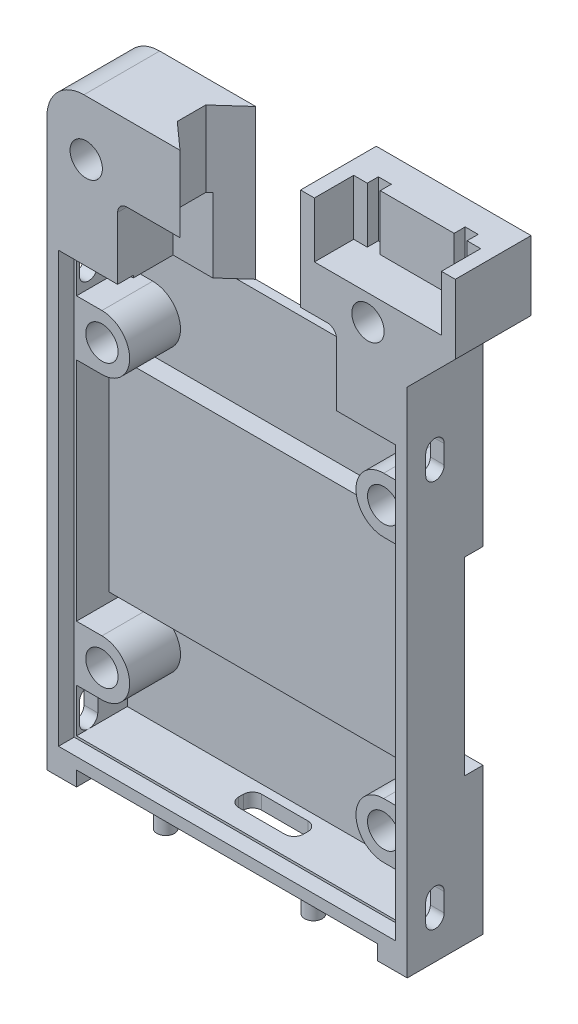
SolidWorks part; units mm, degrees
ref_plane "Front Plane" through (0, 0, 0) normal (0, 0, 1) x (1, 0, 0)
ref_plane "Top Plane" through (0, 0, 0) normal (0, 1, 0) x (1, 0, 0)
ref_plane "Right Plane" through (0, 0, 0) normal (1, 0, 0) x (0, 0, -1)
sketch "Sketch1" plane through (0, 0, 0) normal (0, 0, 1) x (1, 0, 0)
  line L0 (15.25, -20.35) -> (18, -20.35)
  line L1 (-19.5, -32.6) -> (19.5, -32.6)
  line L2 (-19.5, -32.6) -> (-19.5, 31.1)
  line L3 (-19.5, 31.1) -> (19.5, 31.1)
  line L4 (19.5, -32.6) -> (19.5, 31.1)
  line L5 (-15.25, -20.35) -> (-18, -20.35)
  line L6 (15.25, -26.35) -> (18, -26.35)
  line L7 (6.95, 31.1) -> (-15.5, 31.1) construction
  line L8 (-18, -31.1) -> (-18, 29.6)
  line L9 (-18, 29.6) -> (18, 29.6)
  line L10 (18, -31.1) -> (18, 29.6)
  line L11 (-18, -31.1) -> (18, -31.1)
  line L12 (-18, 14.9) -> (18, 14.9)
  line L13 (7.85, 14.9) -> (-4.95, 14.9) construction
  line L14 (-15.25, 4.15) -> (-18, 4.15)
  line L15 (-15.25, 10.15) -> (-18, 10.15)
  line L16 (15.25, 10.15) -> (18, 10.15)
  line L17 (15.25, 4.15) -> (18, 4.15)
  line L18 (-15.25, -26.35) -> (-18, -26.35)
  line L19 (19.5, -34.2) -> (19.5, -18.35) construction
  line L20 (-19.5, -34.2) -> (-19.5, -18.35) construction
  line L21 (15.3, -32.6) -> (-15.3, -32.6) construction
  line L22 (0, 31.1) -> (0, -32.6) construction
  line L23 (9.45, 26.9) -> (24.7, 26.9)
  line L24 (9.45, 26.9) -> (9.45, 33.9)
  line L25 (9.45, 33.9) -> (24.7, 33.9)
  line L26 (24.7, 26.9) -> (24.7, 33.9)
  line L27 (18, 29.6) -> (19.5, 31.1) construction
  line L28 (18.75, 30.35) -> (0, 30.35) construction
  line L29 (9.45, 26.9) -> (7.95, 26.9) construction
  line L30 (-7.95, 31.1) -> (7.95, 31.1)
  line L31 (-7.95, 31.1) -> (-7.95, 29.6)
  line L32 (-7.95, 29.6) -> (7.95, 29.6)
  line L33 (7.95, 31.1) -> (7.95, 29.6)
  line L34 (-7.95, 31.1) -> (7.95, 29.6) construction
  line L35 (-7.95, 29.6) -> (7.95, 31.1) construction
  line L36 (7.95, 26.9) -> (7.95, 29.6) construction
  line L37 (18, 29.6) -> (19.5, 29.6) construction
  line L38 (24.7, 26.4) -> (19.5, 21.2)
  line L39 (9.45, 33.9) -> (7.95, 33.9)
  line L40 (23.2, 33.9) -> (23.2, 26.9)
  line L41 (7.95, 33.9) -> (7.95, 31.1)
  line L42 (24.7, 30.4) -> (23.2, 30.4) construction
  line L43 (24.7, 26.9) -> (19.5, 26.9)
  line L44 (24.7, 26.9) -> (24.7, 26.4)
  line L45 (24.7, 26.4) -> (19.5, 26.4)
  line L46 (19.5, 26.9) -> (19.5, 26.4)
  arc A1 (-15.5, 31.1) -> (-19.5, 27.1) centre (-15.5, 27.1) ccw construction
  arc A3 (-15.5, 31.1) -> (-19.5, 27.1) centre (-15.5, 27.1) ccw
  arc A4 (-15.5, 29.6) -> (-18, 27.1) centre (-15.5, 27.1) ccw
  circle A6 centre (-15.25, -23.35) radius 1.75
  circle A7 centre (15.25, -23.35) radius 1.75
  circle A8 centre (-15.25, 7.15) radius 1.75
  circle A9 centre (15.25, 7.15) radius 1.75
  circle A10 centre (15.25, 25.15) radius 1.75
  circle A11 centre (-15.25, 25.15) radius 1.75
  circle A12 centre (-15.25, -23.35) radius 3
  circle A13 centre (15.25, -23.35) radius 3
  circle A14 centre (15.25, 7.15) radius 3
  circle A15 centre (-15.25, 7.15) radius 3
  dimension "D2" = 1.5
  dimension "D4" = 6
  dimension "D3" = 3.5
  dimension "D5" = 13.75
  dimension "D6" = 15.9
  dimension "D7" = 7
  dimension "D8" = 45
  dimension "D9" = 0.5
  dimension "D1" = 1.5
extrude "Base shape" add sketch "Sketch1" along normal up to surface (8.2 mm away) contours L3 A3 L2 L1 L4 A15 L8 L9 L10 A14 A13 L11 A12 | A15 L15 L8 | A15 L8 L14 | A12 L5 L8 | A12 L8 L18 | A13 L10 L0 | A13 L6 L10 | A14 L10 L16 | A14 L17 L10 | L9 A4 L8 L12 L10 A11 A10 | A4 L9 L8 | L10 A13 | L10 A13 A7 | A12 L8 A6 | L8 A12 | A15 L8 A8 | L8 A15 | L10 A14 | L10 A14 A9 | L33 L3 L31 L9 | L3 L33 L9 L24 | L24 L9 L10 L23 L4 L3 | L24 L23 L10 L9 | L23 L26 L25 L24 L3 L4 | L23 L4 | L3 L24 | L25 L40 L23 L26 | L38 L45 L4 region at (16.8481, -20.9099, 0) region at (17.3601, -20.8437, 0) region at (18.7469, -8.1, 0) region at (17.3601, -25.8563, 0) region at (18.1004, -23.35, 0) region at (17.3601, 4.6437, 0) region at (16.8481, 4.7099, 0) region at (18.1004, 7.15, 0) region at (17.3601, 9.6563, 0) region at (-17.3601, -25.8563, 0) region at (-0.6044, 21.831, 0) region at (-18.1004, -23.35, 0) region at (-17.9169, -23.35, 0) region at (13.725, 28.25, 0) region at (15.3803, 29.9053, 0) region at (-17.3601, -20.8437, 0) region at (22.1, 26.65, 0) region at (17.77, 31.4935, 0) region at (-17.3601, 9.6563, 0) region at (-17.4416, 29.0416, 0) region at (8.7, 30.35, 0) region at (21.2333, 24.6667, 0) region at (23.95, 30.4, 0) region at (-16.8481, 9.5901, 0) region at (-18.1004, 7.15, 0) region at (-17.3601, 4.6437, 0) region at (0, 30.35, 0) region at (8.7, 32.5, 0)
sketch "Sketch3" plane through (19.5, 0, 0) normal (1, 0, 0) x (0, 0, -1)
  line L1 (0, -18.35) -> (-2, -18.35)
  line L2 (0, -18.35) -> (0, 2.15)
  line L3 (0, 2.15) -> (-2, 2.15)
  line L4 (-2, -18.35) -> (-2, 2.15)
  line L5 (0, -18.35) -> (2, -18.35) construction
  line L6 (0, 2.15) -> (2, 2.15) construction
  line L7 (0, -32.6) -> (0, 21.2) construction
  dimension "D1" = 2
extrude "Strap cut" cut sketch "Sketch3" against normal through all
sketch "Sketch4" plane through (0, 31.1, 0) normal (0, 1, 0) x (1, 0, 0)
  line L2 (7.95, 0) -> (-5.0998, 0)
  line L4 (-15.5, 0) -> (7.95, 0) construction
  line L5 (-15.5, -8.2) -> (7.95, -8.2) construction
  line L6 (7.95, -8.2) -> (-5.0998, -8.2)
  line L12 (7.95, -8.3) -> (7.95, 0.1)
  line L13 (7.95, 0.1) -> (-4.9883, 0.1)
  line L14 (-4.9883, 0.1) -> (-7.95, -2.5553)
  line L15 (-7.95, -2.5553) -> (-7.95, -5.6447)
  line L16 (-7.95, -5.6447) -> (-4.9883, -8.3)
  line L17 (-4.9883, -8.3) -> (7.95, -8.3)
  line L18 (7.95, -8.3) -> (7.95, 0.1)
  line L19 (7.95, 0.1) -> (-4.9883, 0.1)
  line L20 (-4.9883, 0.1) -> (-7.95, -2.5553)
  line L21 (-7.95, -2.5553) -> (-7.95, -5.6447)
  line L22 (-7.95, -5.6447) -> (-4.9883, -8.3)
  line L23 (-4.9883, -8.3) -> (7.95, -8.3)
  dimension "D1" = 0.1
extrude "XT60 cut" cut sketch "Sketch4" against normal up to next contours L21 L22 L18 L20 region at (0.4142, 31.1, 4.1)
sketch "Sketch5" plane through (19.5, 0, 0) normal (1, 0, 0) x (0, 0, -1)
  line L1 (-8.2, -32.6) -> (-8.2, 21.2) construction
  line L2 (-6.2, -31.1) -> (-4.2, -31.1)
  line L3 (-6.2, -31.1) -> (-6.2, -27.1)
  line L4 (-6.2, -27.1) -> (-4.2, -27.1)
  line L5 (-4.2, -31.1) -> (-4.2, -27.1)
  line L6 (-8.2, -31.1) -> (0, -31.1) construction
  line L7 (-8.2, 14.9) -> (0, 14.9) construction
  line L8 (-6.2, 14.9) -> (-4.2, 14.9)
  line L9 (-6.2, 14.9) -> (-6.2, 10.9)
  line L10 (-6.2, 10.9) -> (-4.2, 10.9)
  line L11 (-4.2, 14.9) -> (-4.2, 10.9)
  line L14 (-5.2, -27.1) -> (-5.2, -31.1) construction
  line L15 (-5.2, 14.9) -> (-5.2, 10.9) construction
  circle A0 centre (-5.2, -28.1) radius 1
  circle A1 centre (-5.2, -30.1) radius 1
  circle A2 centre (-5.2, 13.9) radius 1
  circle A3 centre (-5.2, 11.9) radius 1
  point P20 (-5.2, -29.1)
  point P31 (-5.2, 12.9)
  dimension "D3" = 4
  dimension "D1" = 2
  dimension "D2" = 2
extrude "Power wires cut" cut sketch "Sketch5" against normal through all contours A2 | A3 | A3 A2 L9 | A3 L11 A2 | A1 | A0 | A1 L5 A0 | A1 A0 L3 region at (19.5, -30.1, 5.2) region at (19.5, -29.1, 5.9766) region at (19.5, -29.1, 4.4234) region at (19.5, -28.1, 5.2) region at (19.5, 13.9, 5.2) region at (19.5, 12.9, 5.9766) region at (19.5, 12.9, 4.4234) region at (19.5, 11.9, 5.2)
sketch "Sketch6" plane through (0, 0, 8.2) normal (0, 0, 1) x (1, 0, 0)
  line L0 (-7.85, 15.9) -> (-7.85, 21.9) construction
  line L1 (-8.85, 22.9) -> (-10.85, 22.9) construction
  line L2 (-11.85, 15.9) -> (-11.85, 21.9) construction
  line L3 (-8.85, 14.9) -> (-10.85, 14.9) construction
  line L4 (-7.85, 15.9) -> (-7.85, 21.9)
  line L5 (-8.85, 22.9) -> (-10.85, 22.9)
  line L6 (-11.85, 15.9) -> (-11.85, 21.9)
  line L7 (-8.85, 14.9) -> (-10.85, 14.9)
  line L8 (7.85, 15.9) -> (7.85, 21.9) construction
  line L9 (8.85, 22.9) -> (10.85, 22.9) construction
  line L10 (11.85, 15.9) -> (11.85, 21.9) construction
  line L11 (8.85, 14.9) -> (10.85, 14.9) construction
  line L12 (7.85, 15.9) -> (7.85, 21.9)
  line L13 (8.85, 22.9) -> (10.85, 22.9)
  line L14 (11.85, 15.9) -> (11.85, 21.9)
  line L15 (8.85, 14.9) -> (10.85, 14.9)
  line L17 (-11.85, 15.9) -> (-7.85, 15.9)
  line L18 (-11.85, 15.9) -> (-11.85, 14.9)
  line L19 (-11.85, 14.9) -> (-7.85, 14.9)
  line L20 (-7.85, 15.9) -> (-7.85, 14.9)
  line L22 (11.85, 15.9) -> (7.85, 15.9)
  line L23 (11.85, 15.9) -> (11.85, 14.9)
  line L24 (11.85, 14.9) -> (7.85, 14.9)
  line L25 (7.85, 15.9) -> (7.85, 14.9)
  line L26 (-18, 14.9) -> (-5.0998, 14.9) construction
  line L27 (11.85, 21.9) -> (7.85, 21.9)
  line L28 (11.85, 21.9) -> (11.85, 22.9)
  line L29 (11.85, 22.9) -> (7.85, 22.9)
  line L30 (7.85, 21.9) -> (7.85, 22.9)
  line L31 (-8.85, 22.9) -> (7.95, 22.9)
  line L32 (-8.85, 22.9) -> (-8.85, 14.9)
  line L33 (-8.85, 14.9) -> (7.95, 14.9)
  line L34 (7.95, 22.9) -> (7.95, 14.9)
  line L35 (7.95, 14.9) -> (18, 14.9) construction
  line L36 (7.95, 14.9) -> (7.95, 33.9) construction
  arc A0 (-8.85, 14.9) -> (-7.85, 15.9) centre (-8.85, 15.9) ccw construction
  arc A1 (-7.85, 21.9) -> (-8.85, 22.9) centre (-8.85, 21.9) ccw construction
  arc A2 (-10.85, 22.9) -> (-11.85, 21.9) centre (-10.85, 21.9) ccw construction
  arc A3 (-11.85, 15.9) -> (-10.85, 14.9) centre (-10.85, 15.9) ccw construction
  arc A4 (-8.85, 14.9) -> (-7.85, 15.9) centre (-8.85, 15.9) ccw
  arc A5 (-7.85, 21.9) -> (-8.85, 22.9) centre (-8.85, 21.9) ccw
  arc A6 (-10.85, 22.9) -> (-11.85, 21.9) centre (-10.85, 21.9) ccw
  arc A7 (-11.85, 15.9) -> (-10.85, 14.9) centre (-10.85, 15.9) ccw
  arc A8 (8.85, 22.9) -> (7.85, 21.9) centre (8.85, 21.9) ccw construction
  arc A9 (11.85, 21.9) -> (10.85, 22.9) centre (10.85, 21.9) ccw construction
  arc A10 (10.85, 14.9) -> (11.85, 15.9) centre (10.85, 15.9) ccw construction
  arc A11 (7.85, 15.9) -> (8.85, 14.9) centre (8.85, 15.9) ccw construction
  arc A12 (8.85, 22.9) -> (7.85, 21.9) centre (8.85, 21.9) ccw
  arc A13 (11.85, 21.9) -> (10.85, 22.9) centre (10.85, 21.9) ccw
  arc A14 (10.85, 14.9) -> (11.85, 15.9) centre (10.85, 15.9) ccw
  arc A15 (7.85, 15.9) -> (8.85, 14.9) centre (8.85, 15.9) ccw
  line M1 (7.95, 33.9) -> (7.95, 14.9)
  line M15 (-5.0998, 14.9) -> (-5.0998, 31.1)
extrude "IO wires cut" cut sketch "Sketch6" against normal blind 6 contours L33 L25 L12 L30 L31 M15 | A5 L4 L20 L31 M15 | L4 A5 L32 L17 | L5 A6 L6 L17 L32 | A7 L18 | L17 A7 L32 | L32 A4 L17 | A4 L20 | A12 L29 L30 M1 | L27 L12 L22 M1 | L22 A15 M1 | A15 L25 L24 L34 | A15 L34 | A15 A14 L22 M1 | A14 L23 | L14 L27 L22 M1 | L27 A13 L13 A12 L34 | A12 L29 M1 region at (-8.3587, 19.2964, 8.2) region at (-8.4256, 15.4756, 8.2) region at (-6.4903, 18.9365, 8.2) region at (-8.0734, 15.1234, 8.2) region at (-10.2516, 15.4213, 8.2) region at (-10.3368, 19.3662, 8.2) region at (-11.6266, 15.1234, 8.2) region at (1.3751, 18.9, 8.2) region at (7.8959, 15.2606, 8.2) region at (7.8959, 22.5394, 8.2) region at (8.1604, 15.056, 8.2) region at (7.9, 18.9, 8.2) region at (7.9098, 15.7354, 8.2) region at (8.1604, 22.744, 8.2) region at (9.8661, 15.4307, 8.2) region at (9.9, 18.9, 8.2) region at (9.8661, 22.3693, 8.2) region at (11.6266, 15.1234, 8.2)
sketch "Sketch7" plane through (-18, 0, 0) normal (1, 0, 0) x (0, 0, -1)
  line L6 (0, -18.35) -> (0, -20.35)
  line L7 (-2, -18.35) -> (0, -18.35)
  line L8 (-2, 2.15) -> (-2, -18.35)
  line L9 (0, 2.15) -> (-2, 2.15)
  line L12 (0, 3.15) -> (-3, 3.15)
  line L13 (-3, 3.15) -> (-3, -19.35)
  line L14 (-3, -19.35) -> (-1, -19.35)
  line L15 (-1, -19.35) -> (-1, -20.35)
  line L16 (-1, -20.35) -> (0, -20.35)
  line L17 (0, 3.15) -> (-1, 3.15)
  line L19 (0, -31.1) -> (-1, -31.1)
  line L22 (0, -31.1) -> (0, -20.35)
  line L23 (0, -20.35) -> (-1, -20.35)
  line L24 (-1, -31.1) -> (-1, -20.35)
  line L25 (0, 3.15) -> (0, 14.9)
  line L26 (0, 14.9) -> (-1, 14.9)
  line L27 (-1, 3.15) -> (-1, 14.9)
  line L28 (-5.2, 14.9) -> (0, 14.9) construction
  line L31 (0, -20.35) -> (0, -18.35) construction
  line L32 (0, 2.15) -> (-2, 2.15) construction
  line M48 (0, -20.35) -> (0, -18.35)
  line M49 (0, -18.35) -> (-2, -18.35)
  line M50 (-2, -18.35) -> (-2, 2.15)
  line M51 (-2, 2.15) -> (0, 2.15)
  line M52 (0, 2.15) -> (0, 4.15)
  line M53 (0, 4.15) -> (-8.2, 4.15)
  line M55 (-8.2, -20.35) -> (0, -20.35)
  dimension "D1" = 1
extrude "Bottom" add sketch "Sketch7" along normal up to surface (36 mm away) contours L27 L25 L26 M53 | L27 L12 M52 M53 | L14 L15 L12 L13 M55 M48 M49 M50 M51 M52 | L24 L19 L22 M55 region at (-18, -8.5273, 2.2091) region at (-18, -25.725, 0.5) region at (-18, 3.65, 0.5) region at (-18, 9.525, 0.5) up to face at (18, -8.1, 2.55)
sketch "Sketch9" plane through (0, 0, 0) normal (0, 0, -1) x (-1, 0, 0)
  circle A0 centre (-15.25, -23.35) radius 1.75 construction
  circle A1 centre (-15.25, 7.15) radius 1.75 construction
  circle A2 centre (15.25, 7.15) radius 1.75 construction
  circle A3 centre (15.25, -23.35) radius 1.75 construction
  circle A4 centre (-15.25, -23.35) radius 1.75
  circle A5 centre (-15.25, 7.15) radius 1.75
  circle A6 centre (15.25, 7.15) radius 1.75
  circle A7 centre (15.25, -23.35) radius 1.75
extrude "Bottom holes" cut sketch "Sketch9" against normal up to next
sketch "Sketch8" plane through (0, 0, 8.2) normal (0, 0, 1) x (1, 0, 0)
  line L0 (-6.2152, 14.9) -> (-18, 14.9) construction
  line L1 (-18.25, 15.15) -> (18.25, 15.15)
  line L2 (-18.25, 15.15) -> (-18.25, -31.35)
  line L3 (-18.25, -31.35) -> (18.25, -31.35)
  line L4 (18.25, 15.15) -> (18.25, -31.35)
  line L5 (-18, 14.9) -> (-18.25, 14.9) construction
  line L6 (-18, 14.9) -> (-18, 15.15) construction
  line L7 (18, 14.9) -> (18.25, 14.9) construction
  line L8 (-18, -31.1) -> (-18, -31.35) construction
  dimension "D1" = 0.25
extrude "PCB cut" cut sketch "Sketch8" against normal blind 1.7
sketch "Sketch11" plane through (0, -32.6, 0) normal (0, -1, 0) x (1, 0, 0)
  line L0 (19.5, 8.2) -> (19.5, 0) construction
  line L1 (-19.5, 8.2) -> (19.5, 8.2)
  line L2 (-19.5, 8.2) -> (-19.5, -1.8)
  line L3 (-19.5, -1.8) -> (19.5, -1.8)
  line L4 (19.5, 8.2) -> (19.5, -1.8)
  line L5 (-19.5, 3.2) -> (19.5, 3.2) construction
  line L6 (0, -1.8) -> (0, 8.2) construction
  line L8 (-2.5, 4.45) -> (2.5, 4.45)
  line L9 (-3.5, 3.45) -> (-3.5, 2.95)
  line L10 (-2.5, 1.95) -> (2.5, 1.95)
  line L11 (3.5, 3.45) -> (3.5, 2.95)
  line L12 (-3.5, 4.45) -> (3.5, 1.95) construction
  line L13 (-3.5, 1.95) -> (3.5, 4.45) construction
  arc A0 (2.5, 4.45) -> (3.5, 3.45) centre (2.5, 3.45) cw
  arc A1 (2.5, 1.95) -> (3.5, 2.95) centre (2.5, 2.95) ccw
  arc A2 (-3.5, 2.95) -> (-2.5, 1.95) centre (-2.5, 2.95) ccw
  arc A3 (-2.5, 4.45) -> (-3.5, 3.45) centre (-2.5, 3.45) ccw
  point P11 (0, 3.2)
  dimension "D4" = 1
  dimension "D1" = 10
  dimension "D2" = 7
  dimension "D3" = 2.5
extrude "Ledbar wires cut" cut sketch "Sketch11" against normal up to next contours L8 A3 L9 A2 L10 A1 L11 A0 region at (0, -32.6, 3.2)
sketch "Sketch13" plane through (0, -32.6, 0) normal (0, -1, 0) x (1, 0, 0)
  line L0 (-19.5, 8.2) -> (19.5, 8.2) construction
  line L1 (19.5, 0) -> (16.3, 0)
  line L2 (19.5, 0) -> (19.5, 8.2)
  line L3 (19.5, 8.2) -> (16.3, 8.2)
  line L4 (16.3, 0) -> (16.3, 8.2)
  line L5 (16.1, -1.8) -> (16.1, 8.2) construction
  line L6 (0, 8.2) -> (0, 0) construction
  line L7 (-19.5, 0) -> (-16.3, 0)
  line L8 (-19.5, 0) -> (-19.5, 8.2)
  line L9 (-19.5, 8.2) -> (-16.3, 8.2)
  line L10 (-16.3, 0) -> (-16.3, 8.2)
  dimension "D1" = 0.2
extrude "Ledbar sides" add sketch "Sketch13" along normal blind 1.6
sketch "Sketch14" plane through (0, -32.6, 0) normal (0, -1, 0) x (1, 0, 0)
  circle A0 centre (8, 6.85) radius 0.95
  circle A1 centre (-8, 6.85) radius 0.95
  dimension "D1" = 1.9
extrude "Ledbar mounts" add sketch "Sketch14" along normal blind 2
sketch "Sketch16" plane through (0, 33.9, 0) normal (0, 1, 0) x (1, 0, 0)
  line L0 (7.95, -6.075) -> (24.7, -6.075) construction
  line L1 (7.95, -8.2) -> (24.7, -8.2) construction
  line L2 (21.725, -2.75) -> (20.325, -2.75)
  line L3 (20.325, -3.95) -> (20.325, -2.75)
  line L4 (9.45, -3.95) -> (23.2, -3.95)
  line L5 (9.45, -3.95) -> (9.45, -8.2)
  line L6 (9.45, -8.2) -> (23.2, -8.2)
  line L7 (23.2, -3.95) -> (23.2, -8.2)
  line L8 (9.45, -3.95) -> (23.2, -8.2) construction
  line L9 (9.45, -8.2) -> (23.2, -3.95) construction
  line L10 (24.7, -8.2) -> (24.7, 0) construction
  line L11 (7.95, -8.2) -> (7.95, 0) construction
  line L12 (16.325, -8.2) -> (16.325, -3.95) construction
  line L13 (11.625, -2.75) -> (11.625, -3.95) construction
  line L14 (10.925, -3.95) -> (12.325, -3.95)
  line L15 (10.925, -3.95) -> (10.925, -2.75)
  line L16 (10.925, -2.75) -> (12.325, -2.75)
  line L17 (12.325, -3.95) -> (12.325, -2.75)
  line L18 (10.925, -2.75) -> (10.925, -8.2) construction
  line L19 (21.725, -3.95) -> (21.725, -2.75)
  point P6 (16.325, -6.075)
  dimension "D1" = 13.75
  dimension "D2" = 4.25
  dimension "D3" = 1.4
  dimension "D4" = 1.2
  dimension "D5" = 4.7
extrude "Balance plug cut" cut sketch "Sketch16" against normal blind 6 contours L7 L4 L5 L6 | L4 L17 L16 L15 | L4 L19 L2 L3 region at (21.025, 33.9, 3.35) region at (16.325, 33.9, 6.075) region at (11.625, 33.9, 3.35)
sketch "Sketch10" [suppressed] plane through (0, 0, 2) normal (0, 0, -1) x (-1, 0, 0)
  line L0 (0, 2.15) -> (0, -18.35) construction
  line L1 (19.5, 2.15) -> (-19.5, 2.15) construction
  line L2 (19.5, -18.35) -> (-19.5, -18.35) construction
  line L3 (19.5, 2.15) -> (19.5, -18.35) construction
  line L4 (-19.5, 1.15) -> (19.5, 1.15)
  line L5 (-19.5, 1.15) -> (-19.5, 0.65)
  line L6 (-19.5, 0.65) -> (19.5, 0.65)
  line L7 (19.5, 1.15) -> (19.5, 0.65)
  line L8 (-19.5, 1.15) -> (19.5, 0.65) construction
  line L9 (-19.5, 0.65) -> (19.5, 1.15) construction
  line L10 (-19.5, 2.15) -> (19.5, 2.15) construction
  line L11 (-19.5, -1.35) -> (19.5, -1.35)
  line L12 (19.5, -0.85) -> (19.5, -1.35)
  line L13 (-19.5, -0.85) -> (19.5, -0.85)
  line L14 (-19.5, -0.85) -> (-19.5, -1.35)
  line L15 (-19.5, -3.35) -> (19.5, -3.35)
  line L16 (19.5, -2.85) -> (19.5, -3.35)
  line L17 (-19.5, -2.85) -> (19.5, -2.85)
  line L18 (-19.5, -2.85) -> (-19.5, -3.35)
  line L19 (-19.5, -5.35) -> (19.5, -5.35)
  line L20 (19.5, -4.85) -> (19.5, -5.35)
  line L21 (-19.5, -4.85) -> (19.5, -4.85)
  line L22 (-19.5, -4.85) -> (-19.5, -5.35)
  line L23 (-19.5, -7.35) -> (19.5, -7.35)
  line L24 (19.5, -6.85) -> (19.5, -7.35)
  line L25 (-19.5, -6.85) -> (19.5, -6.85)
  line L26 (-19.5, -6.85) -> (-19.5, -7.35)
  line L27 (-19.5, -9.35) -> (19.5, -9.35)
  line L28 (19.5, -8.85) -> (19.5, -9.35)
  line L29 (-19.5, -8.85) -> (19.5, -8.85)
  line L30 (-19.5, -8.85) -> (-19.5, -9.35)
  line L31 (-19.5, -11.35) -> (19.5, -11.35)
  line L32 (19.5, -10.85) -> (19.5, -11.35)
  line L33 (-19.5, -10.85) -> (19.5, -10.85)
  line L34 (-19.5, -10.85) -> (-19.5, -11.35)
  line L35 (-19.5, -13.35) -> (19.5, -13.35)
  line L36 (19.5, -12.85) -> (19.5, -13.35)
  line L37 (-19.5, -12.85) -> (19.5, -12.85)
  line L38 (-19.5, -12.85) -> (-19.5, -13.35)
  line L39 (-19.5, -15.35) -> (19.5, -15.35)
  line L40 (19.5, -14.85) -> (19.5, -15.35)
  line L41 (-19.5, -14.85) -> (19.5, -14.85)
  line L42 (-19.5, -14.85) -> (-19.5, -15.35)
  line L43 (-19.5, -17.35) -> (19.5, -17.35)
  line L44 (19.5, -16.85) -> (19.5, -17.35)
  line L45 (-19.5, -16.85) -> (19.5, -16.85)
  line L46 (-19.5, -16.85) -> (-19.5, -17.35)
  point P6 (0, 0.9)
  dimension "D1" = 1
  dimension "D2" = 0.5
  dimension "D4" = 2
  dimension "D3" = 10
extrude "3D print ribs" [suppressed] add sketch "Sketch10" along normal up to surface (2 mm away) up to face at (13.5, 7.15, 0)
sketch "Sketch15" [suppressed] plane through (0, 0, 0) normal (0, 0, -1) x (-1, 0, 0)
  line L0 (-8, -34.6) -> (-8, -32.6) construction
  line L1 (-8.95, -34.6) -> (-7.05, -34.6) construction
  line L2 (-8.95, -32.6) -> (-7.05, -32.6) construction
  line L3 (0, -32.6) -> (0, 14.9) construction
  line L4 (-8.25, -34.6) -> (-7.75, -34.6)
  line L5 (-8.25, -34.6) -> (-8.25, -32.6)
  line L6 (-8.25, -32.6) -> (-7.75, -32.6)
  line L7 (-7.75, -34.6) -> (-7.75, -32.6)
  line L8 (-8.25, -34.6) -> (-7.75, -32.6) construction
  line L9 (-8.25, -32.6) -> (-7.75, -34.6) construction
  line L10 (16.3, -32.6) -> (-16.3, -32.6) construction
  line L11 (-7.95, 14.9) -> (5.0998, 14.9) construction
  line L12 (8.25, -32.6) -> (7.75, -32.6)
  line L13 (7.75, -34.6) -> (7.75, -32.6)
  line L14 (8.25, -34.6) -> (7.75, -34.6)
  line L15 (8.25, -34.6) -> (8.25, -32.6)
  point P6 (-8, -33.6)
  dimension "D1" = 0.5
extrude "3D print led supports" [suppressed] add sketch "Sketch15" against normal up to next
